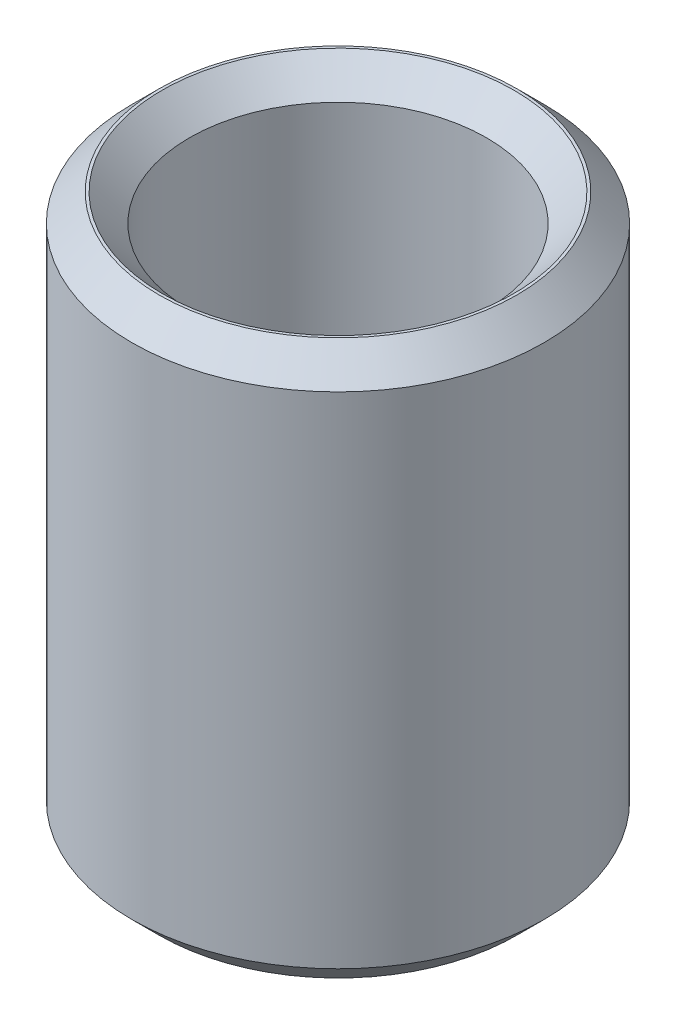
SolidWorks part; units mm, degrees
ref_plane "Front Plane" through (0, 0, 0) normal (0, 0, 1) x (1, 0, 0)
ref_plane "Top Plane" through (0, 0, 0) normal (0, 1, 0) x (1, 0, 0)
ref_plane "Right Plane" through (0, 0, 0) normal (1, 0, 0) x (0, 0, -1)
sketch "Sketch1" plane through (0, 0, 0) normal (0, 1, 0) x (1, 0, 0)
  circle A0 centre (0, 0) radius 27.5
  dimension "SLEEVE_OD" = 55
extrude "Boss-Extrude1" add sketch "Sketch1" along normal blind 73.9349
sketch "Sketch2" plane through (0, 0, 0) normal (0, 1, 0) x (1, 0, 0)
  circle A0 centre (0, 0) radius 19.8157
  dimension "BORE_D" = 39.6314
extrude "Cut-Extrude1" cut sketch "Sketch2" along normal through all
chamfer "Chamfer1" distance 3.6589 angle 45 4 edges at (0, 73.9349, 19.8157) (0, 0, 19.8157) (0, 0, 27.5) (0, 73.9349, 27.5)
